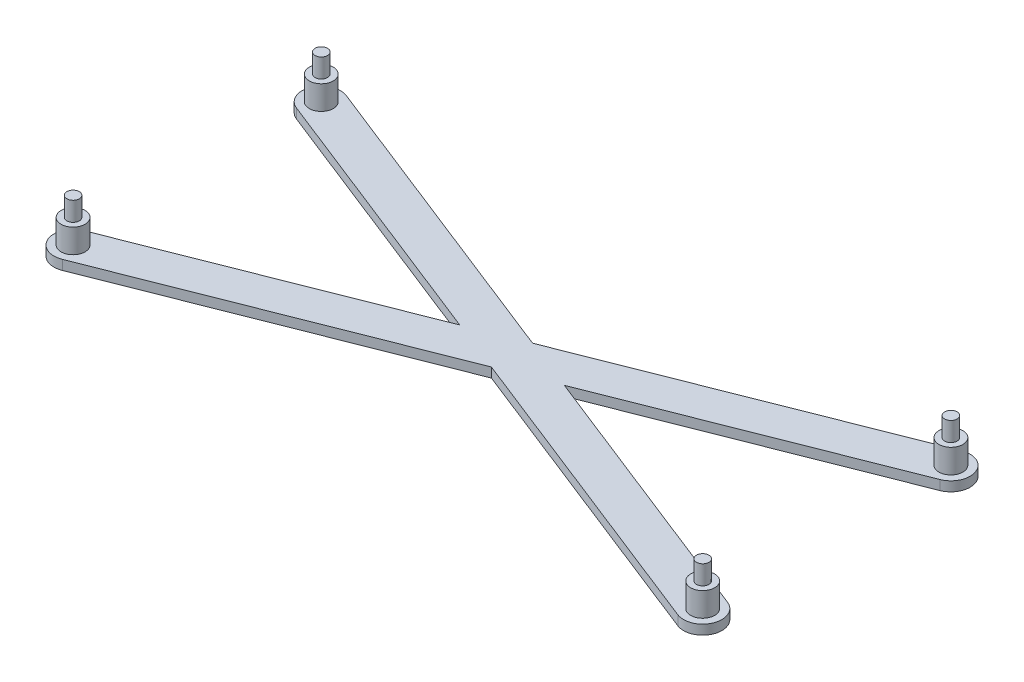
SolidWorks part; units mm, degrees
ref_plane "Front Plane" through (0, 0, 0) normal (0, 0, 1) x (1, 0, 0)
ref_plane "Top Plane" through (0, 0, 0) normal (0, 1, 0) x (1, 0, 0)
ref_plane "Right Plane" through (0, 0, 0) normal (1, 0, 0) x (0, 0, -1)
sketch "Sketch1" plane through (0, 0, 0) normal (0, 1, 0) x (1, 0, 0)
  line L1 (0, 0) -> (70, 0)
  line L2 (0, 0) -> (0, 30)
  line L3 (0, 30) -> (70, 30)
  line L4 (70, 0) -> (70, 30)
  circle A0 centre (2.15, 27.95) radius 0.65
  circle A1 centre (2.15, 2.05) radius 0.65
  circle A2 centre (67.85, 27.95) radius 0.65
  circle A3 centre (67.85, 2.05) radius 0.65
  dimension "D3" = 1.3
  dimension "D4" = 1.3
  dimension "D5" = 1.3
  dimension "D6" = 1.3
  dimension "D1" = 30
  dimension "D2" = 70
  dimension "D7" = 25.9
  dimension "D8" = 2.05
  dimension "D9" = 65.7
  dimension "D10" = 2.15
extrude "Boss-Extrude2" add sketch "Sketch1" along normal blind 1
sketch "Sketch2" plane through (0, 1, 0) normal (0, 1, 0) x (1, 0, 0)
  circle A0 centre (2.15, 27.95) radius 0.65
  circle A1 centre (2.15, 2.05) radius 0.65
  circle A2 centre (67.85, 2.05) radius 0.65
  circle A3 centre (67.85, 27.95) radius 0.65
extrude "Boss-Extrude3" add sketch "Sketch2" along normal mid plane 2
sketch "Sketch4" plane through (0, 2, 0) normal (0, 1, 0) x (1, 0, 0)
  circle A0 centre (2.15, 27.95) radius 0.65
  circle A1 centre (2.15, 2.05) radius 0.65
  circle A2 centre (67.85, 2.05) radius 0.65
  circle A3 centre (67.85, 27.95) radius 0.65
extrude "Boss-Extrude4" add sketch "Sketch4" along normal blind 3.5
sketch "Sketch5" plane through (0, 1, 0) normal (0, 1, 0) x (1, 0, 0)
  circle A0 centre (2.15, 27.95) radius 1.25
  circle A1 centre (2.15, 2.05) radius 1.25
  circle A2 centre (67.85, 2.05) radius 1.25
  circle A3 centre (67.85, 27.95) radius 1.25
  dimension "D1" = 2.5
  dimension "D2" = 2.5
  dimension "D3" = 2.5
  dimension "D4" = 2.5
extrude "Boss-Extrude7" add sketch "Sketch5" along normal blind 2.5
sketch "Sketch6" plane through (0, 1, 0) normal (0, 1, 0) x (1, 0, 0)
  line L0 (1.4165, 26.0894) -> (29.5467, 15)
  line L1 (2.8835, 29.8106) -> (35, 17.1498)
  line L2 (2.8835, 0.1894) -> (35, 12.8502)
  line L3 (1.4165, 3.9106) -> (29.5467, 15)
  line L4 (35, 12.8502) -> (67.1165, 0.1894)
  line L5 (40.4533, 15) -> (68.5835, 3.9106)
  line L6 (35, 17.1498) -> (67.1165, 29.8106)
  line L7 (40.4533, 15) -> (68.5835, 26.0894)
  arc A0 (2.8835, 29.8106) -> (1.4165, 26.0894) centre (2.15, 27.95) ccw
  arc A1 (1.4165, 3.9106) -> (2.8835, 0.1894) centre (2.15, 2.05) ccw
  arc A2 (67.1165, 0.1894) -> (68.5835, 3.9106) centre (67.85, 2.05) ccw
  arc A3 (68.5835, 26.0894) -> (67.1165, 29.8106) centre (67.85, 27.95) ccw
  circle A4 centre (35.8303, 15) radius 70.1561
  dimension "D1" = 4
  dimension "D2" = 4
  dimension "D3" = 4
  dimension "D4" = 4
extrude "Cut-Extrude3" cut sketch "Sketch6" against normal through all both and the other way through all
